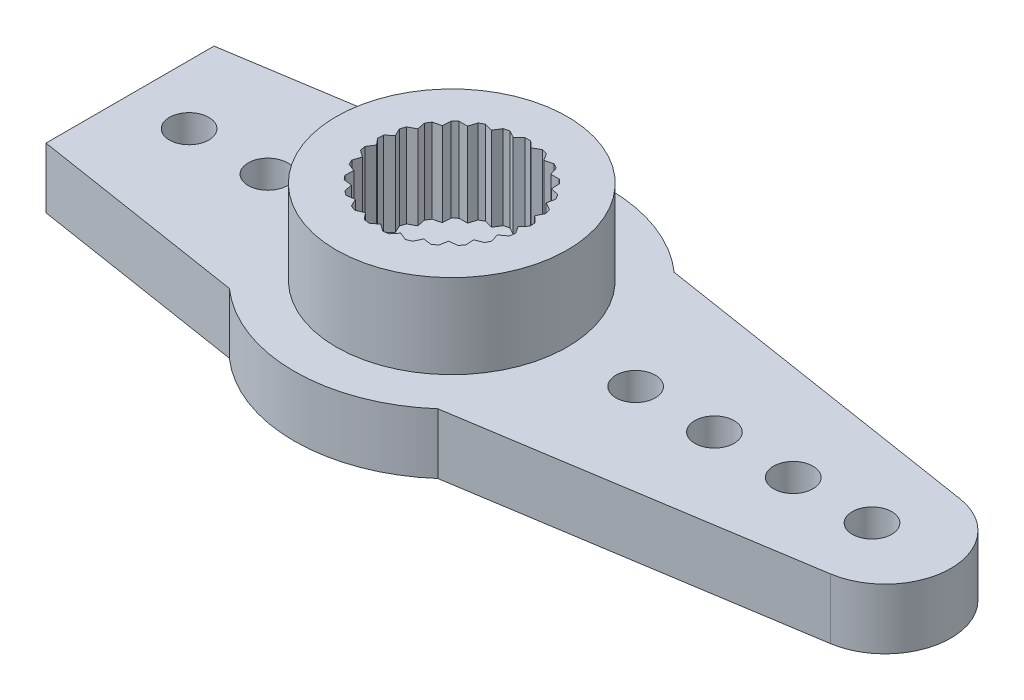
SolidWorks part; units mm, degrees
material "ABS"
ref_plane "Front Plane" through (0, 0, 0) normal (0, 0, 1) x (1, 0, 0)
ref_plane "Top Plane" through (0, 0, 0) normal (0, 1, 0) x (1, 0, 0)
ref_plane "Right Plane" through (0, 0, 0) normal (1, 0, 0) x (0, 0, -1)
sketch "Sketch2" plane through (0, 0, 0) normal (0, 1, 0) x (1, 0, 0)
  circle A0 centre (0, 0) radius 6
  circle A1 centre (0, 0) radius 1.5
  dimension "D1" = 12
  dimension "D2" = 3
extrude "Boss-Extrude1" add sketch "Sketch2" along normal mid plane 2.3
sketch "Sketch3" plane through (0, 1.15, 0) normal (0, 1, 0) x (1, 0, 0)
  line L0 (0, 0) -> (0, 2.9) construction
  line L3 (0, 0) -> (0.376, 2.9763) construction
  line L52 (0.1074, 2.898) -> (0.3384, 2.6787)
  line L53 (-0.1074, 2.898) -> (-0.3384, 2.6787)
  line L54 (0.8248, 2.7802) -> (0.9939, 2.5104)
  line L55 (0.6167, 2.8337) -> (0.3384, 2.6787)
  line L56 (1.4903, 2.4878) -> (1.587, 2.1843)
  line L57 (1.302, 2.5913) -> (0.9939, 2.5104)
  line L58 (2.0621, 2.039) -> (2.0804, 1.721)
  line L59 (1.9055, 2.1861) -> (1.587, 2.1843)
  line L60 (2.5044, 1.4621) -> (2.443, 1.1496)
  line L61 (2.3893, 1.6435) -> (2.0804, 1.721)
  line L62 (2.7894, 0.7934) -> (2.6522, 0.5059)
  line L63 (2.723, 0.9977) -> (2.443, 1.1496)
  line L64 (2.899, 0.0748) -> (2.6947, -0.1695)
  line L65 (2.8855, 0.2892) -> (2.6522, 0.5059)
  line L66 (2.8265, -0.6486) -> (2.5679, -0.8343)
  line L67 (2.8668, -0.4375) -> (2.6947, -0.1695)
  line L68 (2.5765, -1.3311) -> (2.2797, -1.4467)
  line L69 (2.6679, -1.1367) -> (2.5679, -0.8343)
  line L70 (2.1645, -1.93) -> (1.8483, -1.9682)
  line L71 (2.3014, -1.7645) -> (2.2797, -1.4467)
  line L72 (1.6165, -2.4077) -> (1.3007, -2.366)
  line L73 (1.7903, -2.2814) -> (1.8483, -1.9682)
  line L74 (0.967, -2.734) -> (0.6715, -2.6152)
  line L75 (1.1667, -2.655) -> (1.3007, -2.366)
  line L76 (0.2566, -2.8886) -> (0, -2.7)
  line L77 (0.4698, -2.8617) -> (0.6715, -2.6152)
  line L78 (-0.4698, -2.8617) -> (-0.6715, -2.6152)
  line L79 (-0.2566, -2.8886) -> (0, -2.7)
  line L80 (-1.1667, -2.655) -> (-1.3007, -2.366)
  line L81 (-0.967, -2.734) -> (-0.6715, -2.6152)
  line L82 (-1.7903, -2.2814) -> (-1.8483, -1.9682)
  line L83 (-1.6165, -2.4077) -> (-1.3007, -2.366)
  line L84 (-2.3014, -1.7645) -> (-2.2797, -1.4467)
  line L85 (-2.1645, -1.93) -> (-1.8483, -1.9682)
  line L86 (-2.6679, -1.1367) -> (-2.5679, -0.8343)
  line L87 (-2.5765, -1.3311) -> (-2.2797, -1.4467)
  line L88 (-2.8668, -0.4375) -> (-2.6947, -0.1695)
  line L89 (-2.8265, -0.6486) -> (-2.5679, -0.8343)
  line L90 (-2.8855, 0.2892) -> (-2.6522, 0.5059)
  line L91 (-2.899, 0.0748) -> (-2.6947, -0.1695)
  line L92 (-2.723, 0.9977) -> (-2.443, 1.1496)
  line L93 (-2.7894, 0.7934) -> (-2.6522, 0.5059)
  line L94 (-2.3893, 1.6435) -> (-2.0804, 1.721)
  line L95 (-2.5044, 1.4621) -> (-2.443, 1.1496)
  line L96 (-1.9055, 2.1861) -> (-1.587, 2.1843)
  line L97 (-2.0621, 2.039) -> (-2.0804, 1.721)
  line L98 (-1.302, 2.5913) -> (-0.9939, 2.5104)
  line L99 (-1.4903, 2.4878) -> (-1.587, 2.1843)
  line L100 (-0.6167, 2.8337) -> (-0.3384, 2.6787)
  line L101 (-0.8248, 2.7802) -> (-0.9939, 2.5104)
  line L102 (-2.533, 1.6075) -> (-2.3893, 1.6435) construction
  line L103 (-2.533, 1.6075) -> (-2.5044, 1.4621) construction
  line L104 (-2.8532, 0.9271) -> (-2.723, 0.9977) construction
  line L105 (-2.8532, 0.9271) -> (-2.7894, 0.7934) construction
  line L106 (-2.9941, 0.1884) -> (-2.8855, 0.2892) construction
  line L107 (-2.9941, 0.1884) -> (-2.899, 0.0748) construction
  line L108 (-2.9469, -0.5621) -> (-2.8668, -0.4375) construction
  line L109 (-2.9469, -0.5621) -> (-2.8265, -0.6486) construction
  line L110 (0, 3) -> (0.1074, 2.898) construction
  line L111 (0, 2.9) -> (0, 3) construction
  line L112 (0, 3) -> (-0.1074, 2.898) construction
  line L113 (-0.7461, 2.9057) -> (-0.6167, 2.8337) construction
  line L114 (-0.7461, 2.9057) -> (-0.8248, 2.7802) construction
  line L115 (-1.4453, 2.6289) -> (-1.302, 2.5913) construction
  line L116 (-1.4453, 2.6289) -> (-1.4903, 2.4878) construction
  line L117 (-2.0536, 2.1869) -> (-1.9055, 2.1861) construction
  line L118 (-2.0536, 2.1869) -> (-2.0621, 2.039) construction
  line L119 (-2.7145, -1.2773) -> (-2.6679, -1.1367) construction
  line L120 (-2.7145, -1.2773) -> (-2.5765, -1.3311) construction
  line L121 (-2.3115, -1.9123) -> (-2.3014, -1.7645) construction
  line L122 (-2.3115, -1.9123) -> (-2.1645, -1.93) construction
  line L123 (-1.7634, -2.4271) -> (-1.7903, -2.2814) construction
  line L124 (-1.7634, -2.4271) -> (-1.6165, -2.4077) construction
  line L125 (-1.1044, -2.7893) -> (-1.1667, -2.655) construction
  line L126 (-1.1044, -2.7893) -> (-0.967, -2.734) construction
  line L127 (-0.376, -2.9763) -> (-0.4698, -2.8617) construction
  line L128 (-0.376, -2.9763) -> (-0.2566, -2.8886) construction
  line L129 (0.376, -2.9763) -> (0.2566, -2.8886) construction
  line L130 (0.376, -2.9763) -> (0.4698, -2.8617) construction
  line L131 (1.1044, -2.7893) -> (0.967, -2.734) construction
  line L132 (1.1044, -2.7893) -> (1.1667, -2.655) construction
  line L133 (1.7634, -2.4271) -> (1.6165, -2.4077) construction
  line L134 (1.7634, -2.4271) -> (1.7903, -2.2814) construction
  line L135 (2.3115, -1.9123) -> (2.3014, -1.7645) construction
  line L136 (2.3115, -1.9123) -> (2.1645, -1.93) construction
  line L137 (2.7145, -1.2773) -> (2.6679, -1.1367) construction
  line L138 (2.7145, -1.2773) -> (2.5765, -1.3311) construction
  line L139 (2.9469, -0.5621) -> (2.8668, -0.4375) construction
  line L140 (2.9469, -0.5621) -> (2.8265, -0.6486) construction
  line L141 (2.9941, 0.1884) -> (2.8855, 0.2892) construction
  line L142 (2.9941, 0.1884) -> (2.899, 0.0748) construction
  line L143 (2.8532, 0.9271) -> (2.723, 0.9977) construction
  line L144 (2.8532, 0.9271) -> (2.7894, 0.7934) construction
  line L145 (2.533, 1.6075) -> (2.3893, 1.6435) construction
  line L146 (2.533, 1.6075) -> (2.5044, 1.4621) construction
  line L147 (2.0536, 2.1869) -> (1.9055, 2.1861) construction
  line L148 (2.0536, 2.1869) -> (2.0621, 2.039) construction
  line L149 (1.4453, 2.6289) -> (1.302, 2.5913) construction
  line L150 (1.4453, 2.6289) -> (1.4903, 2.4878) construction
  line L151 (0.7461, 2.9057) -> (0.6167, 2.8337) construction
  line L152 (0.7461, 2.9057) -> (0.8248, 2.7802) construction
  circle A0 centre (0, 0) radius 4.4
  circle A1 centre (0, 0) radius 3 construction
  circle A2 centre (0, 0) radius 2.7 construction
  arc A3 (-0.6167, 2.8337) -> (-0.8248, 2.7802) centre (0, 0) ccw
  arc A4 (-0.1074, 2.898) -> (-0.6167, 2.8337) centre (0, 0) ccw construction
  arc A5 (-0.8248, 2.7802) -> (-1.302, 2.5913) centre (0, 0) ccw construction
  arc A6 (-1.302, 2.5913) -> (-1.4903, 2.4878) centre (0, 0) ccw
  arc A7 (-1.4903, 2.4878) -> (-1.9055, 2.1861) centre (0, 0) ccw construction
  arc A8 (-1.9055, 2.1861) -> (-2.0621, 2.039) centre (0, 0) ccw
  arc A9 (-2.0621, 2.039) -> (-2.3893, 1.6435) centre (0, 0) ccw construction
  arc A10 (-2.3893, 1.6435) -> (-2.5044, 1.4621) centre (0, 0) ccw
  arc A11 (-2.5044, 1.4621) -> (-2.723, 0.9977) centre (0, 0) ccw construction
  arc A12 (-2.723, 0.9977) -> (-2.7894, 0.7934) centre (0, 0) ccw
  arc A13 (-2.7894, 0.7934) -> (-2.8855, 0.2892) centre (0, 0) ccw construction
  arc A14 (-2.8855, 0.2892) -> (-2.899, 0.0748) centre (0, 0) ccw
  arc A15 (-2.899, 0.0748) -> (-2.8668, -0.4375) centre (0, 0) ccw construction
  arc A16 (-2.8668, -0.4375) -> (-2.8265, -0.6486) centre (0, 0) ccw
  arc A17 (-2.8265, -0.6486) -> (-2.6679, -1.1367) centre (0, 0) ccw construction
  arc A18 (-2.6679, -1.1367) -> (-2.5765, -1.3311) centre (0, 0) ccw
  arc A19 (-2.5765, -1.3311) -> (-2.3014, -1.7645) centre (0, 0) ccw construction
  arc A20 (-2.3014, -1.7645) -> (-2.1645, -1.93) centre (0, 0) ccw
  arc A21 (-2.1645, -1.93) -> (-1.7903, -2.2814) centre (0, 0) ccw construction
  arc A22 (-1.7903, -2.2814) -> (-1.6165, -2.4077) centre (0, 0) ccw
  arc A23 (-1.6165, -2.4077) -> (-1.1667, -2.655) centre (0, 0) ccw construction
  arc A24 (-1.1667, -2.655) -> (-0.967, -2.734) centre (0, 0) ccw
  arc A25 (-0.967, -2.734) -> (-0.4698, -2.8617) centre (0, 0) ccw construction
  arc A26 (-0.4698, -2.8617) -> (-0.2566, -2.8886) centre (0, 0) ccw
  arc A27 (-0.2566, -2.8886) -> (0.2566, -2.8886) centre (0, 0) ccw construction
  arc A28 (0.2566, -2.8886) -> (0.4698, -2.8617) centre (0, 0) ccw
  arc A29 (0.4698, -2.8617) -> (0.967, -2.734) centre (0, 0) ccw construction
  arc A30 (0.967, -2.734) -> (1.1667, -2.655) centre (0, 0) ccw
  arc A31 (1.1667, -2.655) -> (1.6165, -2.4077) centre (0, 0) ccw construction
  arc A32 (1.6165, -2.4077) -> (1.7903, -2.2814) centre (0, 0) ccw
  arc A33 (1.7903, -2.2814) -> (2.1645, -1.93) centre (0, 0) ccw construction
  arc A34 (2.1645, -1.93) -> (2.3014, -1.7645) centre (0, 0) ccw
  arc A35 (2.3014, -1.7645) -> (2.5765, -1.3311) centre (0, 0) ccw construction
  arc A36 (2.5765, -1.3311) -> (2.6679, -1.1367) centre (0, 0) ccw
  arc A37 (2.6679, -1.1367) -> (2.8265, -0.6486) centre (0, 0) ccw construction
  arc A38 (2.8265, -0.6486) -> (2.8668, -0.4375) centre (0, 0) ccw
  arc A39 (2.8668, -0.4375) -> (2.899, 0.0748) centre (0, 0) ccw construction
  arc A40 (2.899, 0.0748) -> (2.8855, 0.2892) centre (0, 0) ccw
  arc A41 (2.8855, 0.2892) -> (2.7894, 0.7934) centre (0, 0) ccw construction
  arc A42 (2.7894, 0.7934) -> (2.723, 0.9977) centre (0, 0) ccw
  arc A43 (2.723, 0.9977) -> (2.5044, 1.4621) centre (0, 0) ccw construction
  arc A44 (2.5044, 1.4621) -> (2.3893, 1.6435) centre (0, 0) ccw
  arc A45 (2.3893, 1.6435) -> (2.0621, 2.039) centre (0, 0) ccw construction
  arc A46 (2.0621, 2.039) -> (1.9055, 2.1861) centre (0, 0) ccw
  arc A47 (1.9055, 2.1861) -> (1.4903, 2.4878) centre (0, 0) ccw construction
  arc A48 (1.4903, 2.4878) -> (1.302, 2.5913) centre (0, 0) ccw
  arc A49 (1.302, 2.5913) -> (0.8248, 2.7802) centre (0, 0) ccw construction
  arc A50 (0.8248, 2.7802) -> (0.6167, 2.8337) centre (0, 0) ccw
  arc A51 (0.3635, 2.8771) -> (0.1074, 2.898) centre (0, 0) ccw construction
  arc A52 (0.1074, 2.898) -> (-0.1074, 2.898) centre (0, 0) ccw
  arc A53 (0.6167, 2.8337) -> (0.3635, 2.8771) centre (0, 0) ccw construction
  point P84 (0, 0)
  dimension "D1" = 8.8
  dimension "D2" = 5.4
  dimension "D3" = 6
  dimension "D6" = 5.8
  dimension "D4" = 7.2
  dimension "D5" = 25
extrude "Boss-Extrude2" add sketch "Sketch3" along normal blind 3.2
sketch "Sketch4" plane through (0, 0, 0) normal (0, 1, 0) x (1, 0, 0)
  line L0 (0, 0) -> (16, 0) construction
  line L1 (3.9686, 4.5) -> (16.8881, 2.4697)
  line L2 (3.9686, -4.5) -> (16.8881, -2.4697)
  line L3 (16, 0) -> (13, 0) construction
  circle A0 centre (0, 0) radius 6 construction
  arc A1 (3.9686, -4.5) -> (3.9686, 4.5) centre (0, 0) ccw
  arc A2 (16.8881, 2.4697) -> (16.8881, -2.4697) centre (16.5, 0) cw
  circle A3 centre (16, 0) radius 0.75
  circle A4 centre (13, 0) radius 0.75
  circle A5 centre (10, 0) radius 0.75
  circle A6 centre (7, 0) radius 0.75
  dimension "D3" = 2.5
  dimension "D5" = 1.5
  dimension "D2" = 9
  dimension "D7" = 3
  dimension "D4" = 0.5
  dimension "D1" = 16
  dimension "D6" = 4
extrude "Boss-Extrude3" add sketch "Sketch4" along normal mid plane 2.3
pattern_circular "CirPattern1" count 2 over 360 about axis through (0, 4.35, 0) along (0, 1, 0) of "Boss-Extrude3"
sketch "Sketch5" [suppressed] plane through (0, 0, 0) normal (0, 1, 0) x (1, 0, 0)
  line L0 (3, 7) -> (-3, 7) construction
  circle A0 centre (0, 0) radius 10
  circle A1 centre (0, 7) radius 0.75
  circle A2 centre (-3, 7) radius 0.75
  circle A3 centre (3, 7) radius 0.75
  circle A4 centre (7, 3) radius 0.75
  circle A5 centre (7, 0) radius 0.75
  circle A6 centre (7, -3) radius 0.75
  circle A7 centre (3, -7) radius 0.75
  circle A8 centre (0, -7) radius 0.75
  circle A9 centre (-3, -7) radius 0.75
  circle A10 centre (-7, -3) radius 0.75
  circle A11 centre (-7, 0) radius 0.75
  circle A12 centre (-7, 3) radius 0.75
  circle A13 centre (0, 0) radius 1.5 construction
  circle A14 centre (0, 0) radius 1.5
  point P8 (0, 7)
  point P31 (0, 0)
  dimension "D1" = 1.5
  dimension "D3" = 2.25
  dimension "D4" = 6
  dimension "D2" = 7
  dimension "D5" = 4
extrude "Boss-Extrude4" [suppressed] add sketch "Sketch5" along normal mid plane 2.3
sketch "Sketch6" plane through (0, -1.15, 0) normal (0, -1, 0) x (1, 0, 0)
  line L2 (-12.25, 0) -> (-12.25, 5.9327)
  line L3 (-12.25, 5.9327) -> (-21.2932, 5.9327)
  line L4 (-21.2932, 0) -> (-21.2932, 5.9327)
  line L6 (-21.2932, 0) -> (-21.2932, -7.3716)
  line L7 (-21.2932, -7.3716) -> (-12.25, -7.3716)
  line L8 (-12.25, 0) -> (-12.25, -7.3716)
  circle A0 centre (-13, 0) radius 0.75 construction
extrude "Cut-Extrude1" cut sketch "Sketch6" against normal blind 10
equation "\"N_hole\"= 4"
equation "\"N_horn\"= 2"
equation "\"D6@Sketch4\"=\"N_hole\""
equation "\"D1@CirPattern1\"=\"N_horn\""
equation "\"D1@Sketch4\"=(\"N_hole\" - 1) *3 +7"
